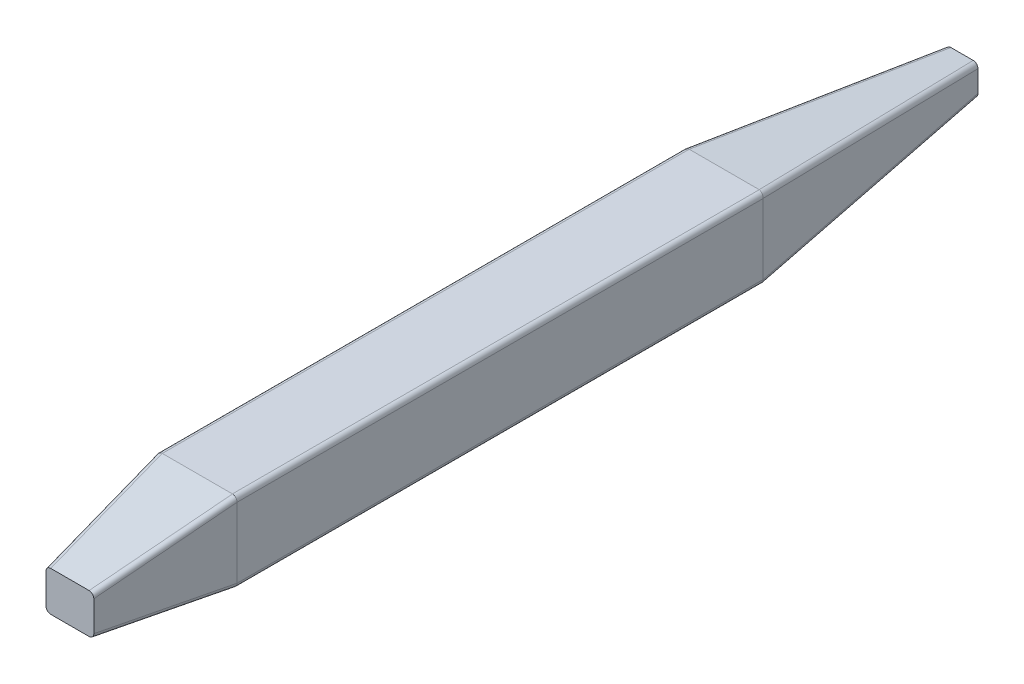
SolidWorks part; units mm, degrees
ref_plane "Front Plane" through (0, 0, 0) normal (0, 0, 1) x (1, 0, 0)
ref_plane "Top Plane" through (0, 0, 0) normal (0, 1, 0) x (1, 0, 0)
ref_plane "Right Plane" through (0, 0, 0) normal (1, 0, 0) x (0, 0, -1)
sketch "Sketch1" plane through (0, 0, 0) normal (1, 0, 0) x (0, 0, -1)
  line L0 (711.2, -15.875) -> (332.0236, -63.5)
  line L1 (711.2, 63.5) -> (-711.2, 63.5)
  line L2 (711.2, 63.5) -> (711.2, -63.5)
  line L3 (711.2, -63.5) -> (-711.2, -63.5)
  line L4 (-711.2, 63.5) -> (-711.2, -63.5)
  line L5 (711.2, 63.5) -> (-711.2, -63.5) construction
  line L6 (711.2, -63.5) -> (-711.2, 63.5) construction
  line L7 (-406.4, -63.5) -> (-406.4, 63.5) construction
  line L8 (332.0236, 63.5) -> (711.2, 33.3925)
  line L9 (-711.2, 19.05) -> (-508, 63.5)
  line L10 (-711.2, -44.45) -> (-508, -63.5)
  line L11 (-508, 63.5) -> (-508, -63.5) construction
  point P0 (0, 0)
  point P9 (-406.4, -63.5)
  point P12 (-508, -63.5)
  point P14 (-531.9954, 63.5)
  point P15 (-711.2, 19.05)
  point P20 (-711.2, -44.45)
  dimension "D1" = 127
  dimension "D2" = 1422.4
  dimension "D3" = 63.5
  dimension "D4" = 44.45
  dimension "D5" = 304.8
  dimension "D6" = 203.2
extrude "Boss-Extrude2" add sketch "Sketch1" along normal blind 127 contours L3 L1 | L1 region at (0, 0.0978, 28.0141)
chamfer "Chamfer1" distance 381 distance2 38.1 1 edges at (127, 8.7588, -711.2) first distance on face at (127, -0.9853, 43.9941)
chamfer "Chamfer2" distance 38.1 distance2 381 1 edges at (0, 8.7588, -711.2) first distance on face at (44.45, 8.7588, -711.2)
chamfer "Chamfer3" distance 25.4 distance2 203.2 1 edges at (127, -12.7, 711.2) first distance on face at (63.5, -12.7, 711.2)
chamfer "Chamfer4" distance 203.2 distance2 25.4 1 edges at (0, -12.7, 711.2) first distance on face at (0, -4.2333, 296.3333)
fillet "Fillet1" radius 7.62 12 edges at (0, -63.5, 88.9) (127, -63.5, 88.9) (0, 63.5, 88.9) (127, 63.5, 88.9) (107.8588, -39.6875, -521.6118) (107.8588, 48.4463, -521.6118) (19.1412, -39.6875, -521.6118) (19.1412, 48.4463, -521.6118) (12.7, -53.975, 609.6) (114.3, -53.975, 609.6) (12.7, 41.275, 609.6) (114.3, 41.275, 609.6)
